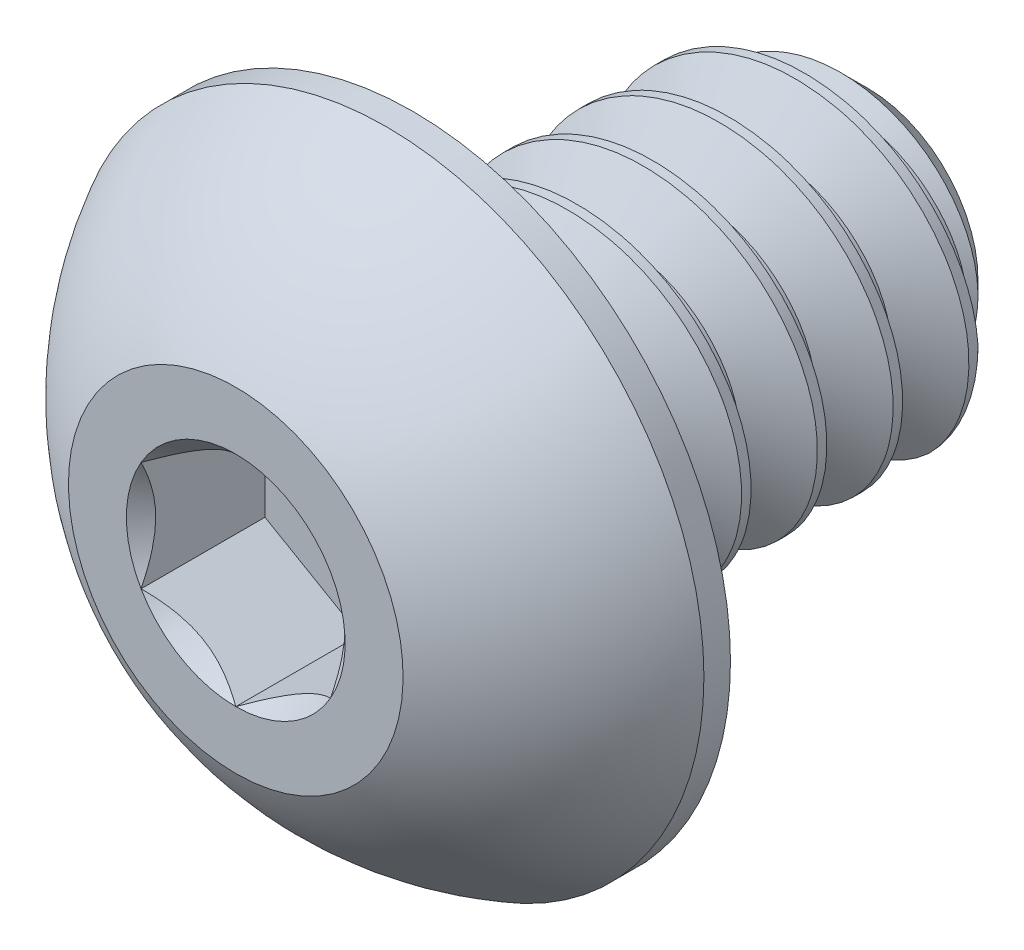
SolidWorks part; units mm, degrees
ref_plane "Front" through (0, 0, 0) normal (0, 0, 1) x (1, 0, 0)
ref_plane "Top" through (0, 0, 0) normal (0, 1, 0) x (1, 0, 0)
ref_plane "Right" through (0, 0, 0) normal (1, 0, 0) x (0, 0, -1)
sketch "Sketch1" plane through (0, 0, 0) normal (1, 0, 0) x (0, 0, -1)
  line L2 (1.8542, 1.7526) -> (6.6167, 1.7526)
  line L3 (6.6167, 1.7526) -> (6.6167, 0)
  line L4 (6.6167, 0) -> (1.8542, 0)
  line L6 (1.5761, 3.3274) -> (1.8542, 3.3274) construction
  line L7 (6.6167, 1.7526) -> (6.6167, -1.7526) construction
  line L8 (0, 0) -> (1.8542, 0) construction
  line L9 (1.8542, 3.3274) -> (1.8542, -3.3274) construction
  line L11 (1.8542, 1.7526) -> (1.8542, 0)
  line L13 (0, 0.9922) -> (0, -0.9922) construction
  line L14 (0, 0.9922) -> (0, 1.7526) construction
  arc A3 (0, 1.7526) -> (1.5761, 3.3274) centre (3.326, 0) cw construction
  dimension "D1" = 0.2781
revolve "Revolve1" add sketch "Sketch1" angle 360 mid plane about L4
sketch "Sketch3" plane through (0, 0, -6.6167) normal (0, 0, -1) x (-1, 0, 0)
  circle A0 centre (0, 0) radius 1.7526
curve "Helix/Spiral1" pitch 0.7937 height 5.5563 radius 1.7526 centre (0, 0, -6.6167) axis (0, 0, 1) start towards (0, 1, 0)
sketch "Sketch2" plane through (0, 0, 0) normal (1, 0, 0) x (0, 0, -1)
  line L0 (6.6167, 1.7526) -> (7.3112, 1.7526)
  line L1 (7.3112, 1.7526) -> (7.0136, 1.237)
  line L2 (7.0136, 1.237) -> (6.9144, 1.237)
  line L3 (6.9144, 1.237) -> (6.6167, 1.7526)
  line L4 (6.7655, 1.4948) -> (7.1624, 1.4948) construction
  dimension "D1" = 60
  dimension "D2" = 0.0992
  dimension "D3" = 0.3969
chamfer "Chamfer1" distance 0.5953 angle 45 1 edges at (0, 1.7526, -6.6167)
sweep "Cut-Sweep1" cut profiles "Sketch2" path "Helix/Spiral1" align with end faces yes
sketch "Sketch7" plane through (0, 0, 0) normal (1, 0, 0) x (0, 0, -1)
  line L6 (1.5761, 3.3274) -> (1.8542, 3.3274) construction
  line L8 (0, 0) -> (1.8542, 0) construction
  line L11 (1.8542, 3.3274) -> (1.8542, -3.3274) construction
  line L12 (1.5761, 3.3274) -> (1.8542, 3.3274)
  line L13 (0, 0) -> (1.8542, 0)
  line L14 (0, 0.9922) -> (0, -0.9922) construction
  line L15 (1.8542, 3.3274) -> (1.8542, 0)
  line L16 (0, 1.7526) -> (0, 0)
  arc A2 (1.5761, 3.3274) -> (0, 1.7526) centre (3.326, 0) ccw construction
  arc A3 (1.5761, 3.3274) -> (0, 1.7526) centre (3.326, 0) ccw
revolve "Revolve2" add sketch "Sketch7" angle 360 mid plane about L13
sketch "Sketch5" plane through (0, 0, 0) normal (0, 0, 1) x (1, 0, 0)
  line L1 (0.9922, -0.5728) -> (0.9922, 0.5728)
  line L2 (0.9922, 0.5728) -> (0, 1.1457)
  line L3 (0, 1.1457) -> (-0.9922, 0.5728)
  line L4 (-0.9922, 0.5728) -> (-0.9922, -0.5728)
  line L5 (-0.9922, -0.5728) -> (0, -1.1457)
  line L6 (0, -1.1457) -> (0.9922, -0.5728)
  circle A0 centre (0, 0) radius 0.9922 construction
extrude "Cut-Extrude2" cut sketch "Sketch5" against normal blind 1.2979
sketch "Sketch6" plane through (0, 0, 0) normal (0, 0, 1) x (1, 0, 0)
  circle A0 centre (0, 0) radius 1.1457
extrude "Cut-Extrude3" cut sketch "Sketch6" against normal blind 1.2979 draft 45
sketch "Sketch9" [suppressed] plane through (0, 0, -1.4986) normal (0, 0, 1) x (1, 0, 0)
  circle A2 centre (0, 0) radius 1.4224
extrude "Boss-Extrude2" [suppressed] add sketch "Sketch9" against normal offset from surface (12.7 mm away) 31.75 up to face at (0, 1.1573, -6.6167)
sketch "Sketch10" plane through (0, 0, 0) normal (1, 0, 0) x (0, 0, -1)
  line L0 (6.6167, 1.7526) -> (6.6167, -1.7526) construction
  point P0 (5.4261, -1.7526)
  dimension "D1" = 1.1906
equation "\"D3@Helix/Spiral1\" = \"Lg@Sketch1\" + \"D4@Helix/Spiral1\""
equation "\"D2@Sketch2\" = \"D4@Helix/Spiral1\" * .125"
equation "\"D3@Sketch2\" = \"D4@Helix/Spiral1\" * .5"
equation "\"D1@Chamfer1\" = \"D4@Helix/Spiral1\" * .75"
equation "\"D1@Cut-Extrude2\" = \"Head Ht@Sketch1\" * .7"
equation "\"D1@Sketch1\" = \"Head Ht@Sketch1\" * .15"
equation "\"D1@Sketch10\" = \"D4@Helix/Spiral1\" * 1.5"
equation "\"D1@Cut-Extrude3\" = \"D1@Cut-Extrude2\""
